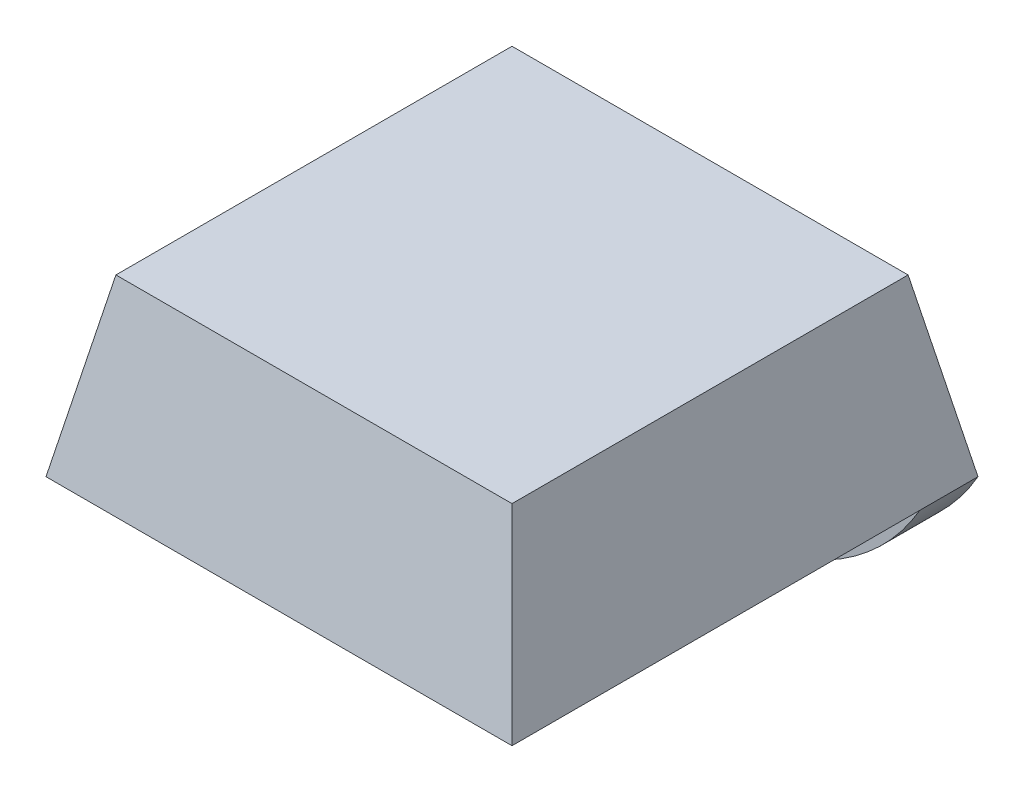
SolidWorks part; units mm, degrees
ref_plane "Front Plane" through (0, 0, 0) normal (0, 0, 1) x (1, 0, 0)
ref_plane "Top Plane" through (0, 0, 0) normal (0, 1, 0) x (1, 0, 0)
ref_plane "Right Plane" through (0, 0, 0) normal (1, 0, 0) x (0, 0, -1)
sketch "Sketch1" plane through (0, 0, 0) normal (0, 1, 0) x (1, 0, 0)
  line L1 (0, 0) -> (8, 0)
  line L2 (0, 0) -> (0, 8)
  line L3 (0, 8) -> (8, 8)
  line L4 (8, 0) -> (8, 8)
  dimension "D1" = 8
  dimension "D2" = 8
extrude "Boss-Extrude1" add sketch "Sketch1" along normal blind 3
sketch "Sketch2" plane through (0, 0, 0) normal (0, 0, 1) x (1, 0, 0)
  line L0 (0, 0) -> (0.6, 3)
  line L1 (0, 3) -> (8, 3) construction
  line L2 (0.6, 3) -> (0, 3)
  line L3 (0, 3) -> (0, 0)
  line L4 (8, 0) -> (7.4, 3)
  line L5 (7.4, 3) -> (8, 3)
  line L6 (8, 3) -> (8, 0)
  dimension "D1" = 0.6
  dimension "D2" = 0.6
extrude "Cut-Extrude1" cut sketch "Sketch2" against normal through all both and the other way through all
sketch "Sketch3" plane through (0, 0, 0) normal (1, 0, 0) x (0, 0, -1)
  line L0 (0, 0) -> (0.6, 3)
  line L1 (8, 3) -> (0, 3) construction
  line L2 (0.6, 3) -> (0, 3)
  line L3 (0, 3) -> (0, 0)
  line L4 (8, 3) -> (7.4, 3)
  line L5 (7.4, 3) -> (8, 0)
  line L6 (8, 3) -> (8, 0)
  dimension "D1" = 0.6
  dimension "D2" = 0.6
extrude "Cut-Extrude2" cut sketch "Sketch3" along normal blind 11
sketch "Sketch4" plane through (0, 0, 0) normal (0, -1, 0) x (1, 0, 0)
  line L0 (8, 0) -> (8, -8) construction
  line L3 (0, 0) -> (8, 0) construction
  circle A0 centre (4, -3.75) radius 1.8
  dimension "D1" = 3.6
  dimension "D2" = 4
  dimension "D3" = 3.75
extrude "Cut-Extrude3" cut sketch "Sketch4" against normal blind 0.8
sketch "Sketch5" plane through (0, 0, 0) normal (0, -1, 0) x (1, 0, 0)
  line L0 (8, 0) -> (8, -8) construction
  line L1 (0, -8) -> (8, -8)
  line L2 (0, -8) -> (0, -7)
  line L3 (0, -7) -> (8, -7)
  line L4 (8, -8) -> (8, -7)
  dimension "D1" = 1
extrude "Boss-Extrude2" add sketch "Sketch5" along normal blind 2
fillet "Fillet1" radius 4 2 edges at (8, -2, -7.5) (0, -2, -7.5)
